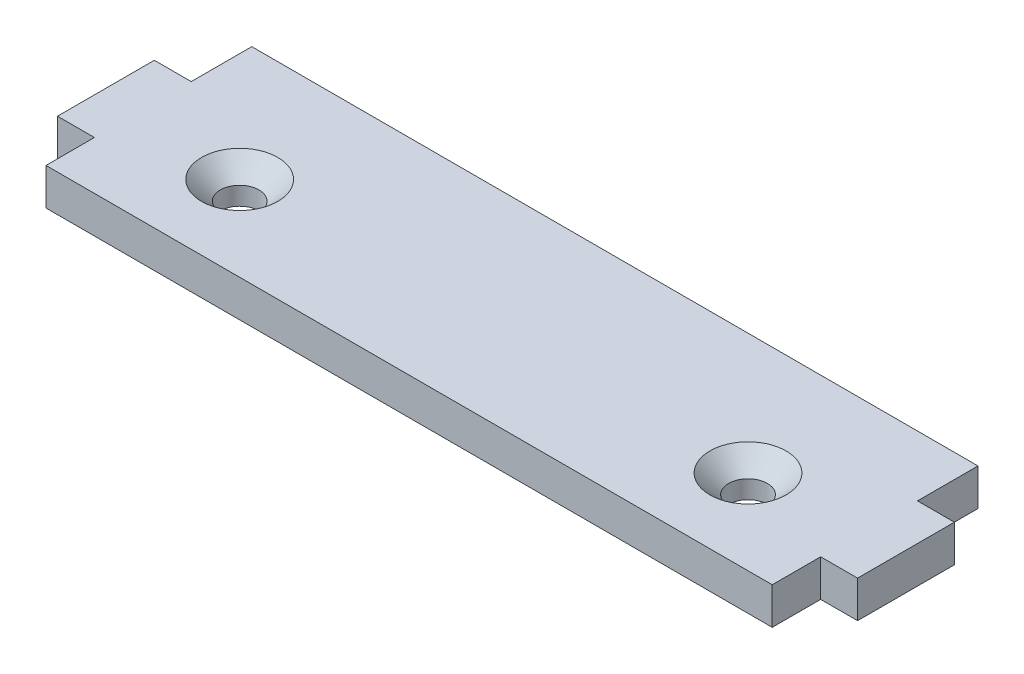
SolidWorks part; units mm, degrees
ref_plane "Front Plane" through (0, 0, 0) normal (0, 0, 1) x (1, 0, 0)
ref_plane "Top Plane" through (0, 0, 0) normal (0, 1, 0) x (1, 0, 0)
ref_plane "Right Plane" through (0, 0, 0) normal (1, 0, 0) x (0, 0, -1)
sketch "Sketch1" plane through (0, 0, 0) normal (0, 1, 0) x (1, 0, 0)
  line L0 (3.05, 12) -> (0, 7)
  line L1 (0, 0) -> (66.1, 0)
  line L2 (0, 0) -> (0, 17)
  line L3 (0, 17) -> (66.1, 17)
  line L4 (66.1, 0) -> (66.1, 17)
  line L7 (0, 12) -> (3.05, 12)
  line L8 (3.05, 17) -> (3.05, 12)
  line L11 (66.1, 12) -> (63.05, 12)
  line L12 (63.05, 17) -> (63.05, 12)
  line L13 (0, 0) -> (12.05, 0)
  line L14 (0, 0) -> (0, 7)
  line L15 (0, 7) -> (12.05, 7)
  line L16 (12.05, 0) -> (12.05, 7)
  line L17 (66.1, 0) -> (54.05, 0)
  line L18 (66.1, 0) -> (66.1, 7)
  line L19 (66.1, 7) -> (54.05, 7)
  line L20 (54.05, 0) -> (54.05, 7)
  line L21 (63.05, 12) -> (66.1, 7)
  line L23 (66.1, 0) -> (63.05, 0)
  line L24 (66.1, 0) -> (66.1, 4)
  line L25 (66.1, 4) -> (63.05, 4)
  line L26 (63.05, 0) -> (63.05, 4)
  line L27 (0, 0) -> (3.05, 0)
  line L28 (0, 0) -> (0, 4)
  line L29 (0, 4) -> (3.05, 4)
  line L30 (3.05, 0) -> (3.05, 4)
  circle A0 centre (12.05, 7) radius 1.5
  circle A1 centre (54.05, 7) radius 1.5
  dimension "D9" = 3
  dimension "D12" = 3
  dimension "D1" = 17
  dimension "D2" = 66.1
  dimension "D3" = 5
  dimension "D4" = 3.05
  dimension "D5" = 5
  dimension "D6" = 3.05
  dimension "D7" = 12.05
  dimension "D8" = 7
  dimension "D10" = 7
  dimension "D11" = 12.05
  dimension "D13" = 5
  dimension "D14" = 58.617
  dimension "D15" = 5
  dimension "D16" = 58.617
  dimension "D17" = 4
  dimension "D18" = 3.05
  dimension "D19" = 4
  dimension "D20" = 3.05
extrude "Boss-Extrude1" add sketch "Sketch1" along normal blind 3.05 contours L12 L3 L8 L7 L2 L1 L4 L11 | A0 L15 L2 L1 L16 | A1 L20 L1 L4 L19 | L11 L21 L4 | L7 L2 L0 region at (33.05, 0, -9.2191) region at (1.0167, 0, -10.3333) region at (6.6697, 0, -3.6881) region at (65.0833, 0, -10.3333) region at (59.4303, 0, -3.6881)
hole_wizard "CSK for M3 Flat Head Machine Screw1" positions "Sketch4" profile "Sketch5" countersink size "M3" standard "ANSI Metric" end condition through all
sketch "Sketch4" plane through (0, 3.05, 0) normal (0, 1, 0) x (1, 0, 0)
  point P0 (12.05, 7)
sketch "Sketch5" plane through (12.05, 3.05, -7) normal (1, 0, 0) x (0, 0, 1)
  line L0 (0, 0) -> (0, 3.05)
  line L1 (0, 3.05) -> (1.6, 3.05)
  line L2 (1.6, 3.05) -> (1.6, 1.55)
  line L3 (1.6, 1.55) -> (3.15, 0)
  line L5 (3.15, 0) -> (0, 0)
  line L6 (-1.6, 1.55) -> (-3.15, 0) construction
  line L11 (0, -6.35) -> (0, 107.95) construction
  dimension "Thru Hole Dia." = 3.2
  dimension "Thru Hole Depth" = 3.05
  dimension "Near C'Sink Dia." = 6.3
  dimension "Near C'Sink Angle" = 90
hole_wizard "CSK for M3 Flat Head Machine Screw2" positions "Sketch6" profile "Sketch7" countersink size "M3" standard "ANSI Metric" end condition through all
sketch "Sketch6" plane through (0, 3.05, 0) normal (0, 1, 0) x (1, 0, 0)
  point P0 (54.05, 7)
sketch "Sketch7" plane through (54.05, 3.05, -7) normal (1, 0, 0) x (0, 0, 1)
  line L0 (0, 0) -> (0, 3.05)
  line L1 (0, 3.05) -> (1.6, 3.05)
  line L2 (1.6, 3.05) -> (1.6, 1.55)
  line L3 (1.6, 1.55) -> (3.15, 0)
  line L5 (3.15, 0) -> (0, 0)
  line L6 (-1.6, 1.55) -> (-3.15, 0) construction
  line L11 (0, -6.35) -> (0, 107.95) construction
  dimension "Thru Hole Dia." = 3.2
  dimension "Thru Hole Depth" = 3.05
  dimension "Near C'Sink Dia." = 6.3
  dimension "Near C'Sink Angle" = 90
